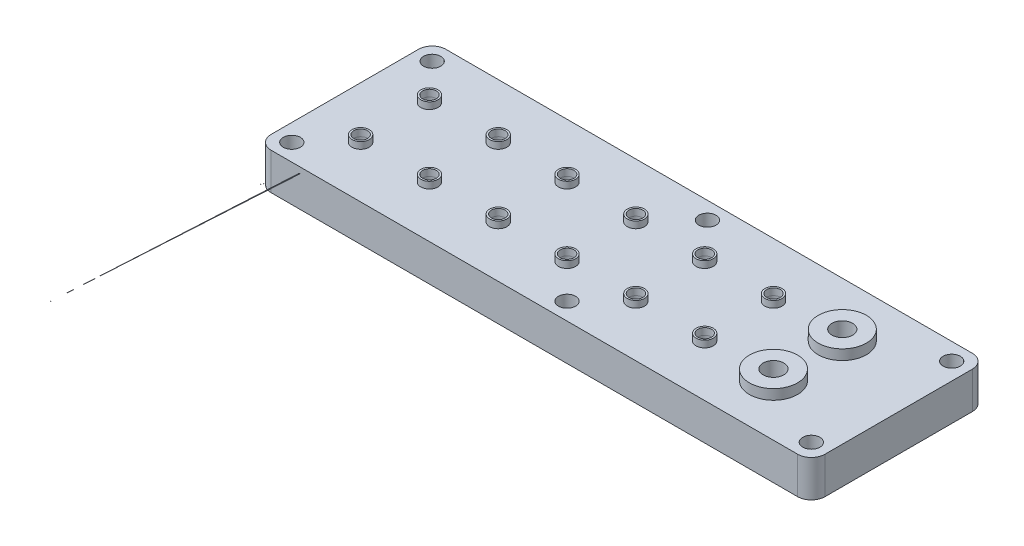
SolidWorks part; units mm, degrees
material "PE High Density"
ref_plane "Front Plane" through (0, 0, 0) normal (0, 0, 1) x (1, 0, 0)
ref_plane "Top Plane" through (0, 0, 0) normal (0, 1, 0) x (1, 0, 0)
ref_plane "Right Plane" through (0, 0, 0) normal (1, 0, 0) x (0, 0, -1)
sketch "Sketch1" plane through (0, 0, 0) normal (0, 1, 0) x (1, 0, 0)
  line L1 (0, 0) -> (161, 0)
  line L2 (0, 0) -> (0, 50.8)
  line L3 (0, 50.8) -> (161, 50.8)
  line L4 (161, 0) -> (161, 50.8)
  dimension "D1" = 161
  dimension "D2" = 50.8
extrude "Boss-Extrude1" add sketch "Sketch1" along normal blind 10.7
sketch "Sketch2" plane through (0, 10.7, 0) normal (0, 1, 0) x (1, 0, 0)
  line L0 (0, 50.8) -> (0, 0) construction
  line L2 (0, 0) -> (161, 0) construction
  circle A0 centre (15, 15) radius 2
  circle A1 centre (15, 35) radius 2
  circle A2 centre (35, 15) radius 2
  circle A3 centre (35, 35) radius 2
  circle A4 centre (55, 35) radius 2
  circle A5 centre (55, 15) radius 2
  circle A6 centre (75, 35) radius 2
  circle A7 centre (75, 15) radius 2
  circle A8 centre (95, 35) radius 2
  circle A9 centre (95, 15) radius 2
  circle A10 centre (115, 35) radius 2
  circle A11 centre (115, 15) radius 2
  circle A12 centre (135, 35) radius 2
  circle A13 centre (135, 15) radius 2
  dimension "D1" = 4
  dimension "D4" = 20
  dimension "D8" = 20
  dimension "D30" = 4
  dimension "D31" = 4
  dimension "D32" = 4
  dimension "D33" = 4
  dimension "D34" = 4
  dimension "D35" = 4
  dimension "D36" = 4
  dimension "D37" = 4
  dimension "D38" = 4
  dimension "D39" = 4
  dimension "D40" = 4
  dimension "D41" = 4
  dimension "D42" = 4
  dimension "D2" = 15
  dimension "D3" = 15
  dimension "D5" = 15
  dimension "D6" = 20
  dimension "D7" = 15
  dimension "D9" = 20
  dimension "D10" = 20
  dimension "D11" = 20
  dimension "D12" = 20
  dimension "D13" = 20
  dimension "D14" = 20
  dimension "D15" = 20
  dimension "D16" = 15
  dimension "D17" = 15
  dimension "D18" = 20
  dimension "D19" = 15
  dimension "D20" = 20
  dimension "D21" = 20
  dimension "D22" = 20
  dimension "D23" = 20
  dimension "D24" = 20
  dimension "D25" = 15
  dimension "D26" = 20
  dimension "D27" = 20
  dimension "D28" = 20
  dimension "D29" = 15
extrude "Cut-Extrude2" cut sketch "Sketch2" against normal through all and the other way blind 1.45
sketch "Sketch3" plane through (0, 0, 0) normal (0, -1, 0) x (-1, 0, 0)
  line L0 (0, 50.8) -> (0, 0) construction
  line L1 (-14.5, 12.5) -> (-135.5, 12.5)
  line L2 (-12.5, 14.5) -> (-12.5, 15.5)
  line L3 (-14.5, 17.5) -> (-135.5, 17.5)
  line L4 (-137.5, 14.5) -> (-137.5, 15.5)
  line L5 (-14.5, 32.5) -> (-135.5, 32.5)
  line L6 (-12.5, 34.5) -> (-12.5, 35.5)
  line L7 (-14.5, 37.5) -> (-135.5, 37.5)
  line L8 (-137.5, 34.5) -> (-137.5, 35.5)
  line L10 (-161, 50.8) -> (0, 50.8) construction
  arc A0 (-14.5, 12.5) -> (-12.5, 14.5) centre (-14.5, 14.5) ccw
  arc A1 (-12.5, 15.5) -> (-14.5, 17.5) centre (-14.5, 15.5) ccw
  arc A2 (-14.5, 32.5) -> (-12.5, 34.5) centre (-14.5, 34.5) ccw
  arc A3 (-12.5, 35.5) -> (-14.5, 37.5) centre (-14.5, 35.5) ccw
  arc A4 (-135.5, 37.5) -> (-137.5, 35.5) centre (-135.5, 35.5) ccw
  arc A5 (-137.5, 34.5) -> (-135.5, 32.5) centre (-135.5, 34.5) ccw
  arc A6 (-137.5, 15.5) -> (-135.5, 17.5) centre (-135.5, 15.5) cw
  arc A7 (-135.5, 12.5) -> (-137.5, 14.5) centre (-135.5, 14.5) cw
  point P14 (-12.5, 12.5)
  point P17 (-12.5, 17.5)
  point P20 (-12.5, 32.5)
  point P23 (-12.5, 37.5)
  dimension "D2" = 33.3
  dimension "D7" = 2
  dimension "D1" = 5
  dimension "D3" = 13.3
  dimension "D4" = 12.5
  dimension "D5" = 137.5
  dimension "D6" = 5
  dimension "D9" = 12.5
  dimension "D10" = 137.5
extrude "Cut-Extrude3" cut sketch "Sketch3" against normal blind 3.5
sketch "Sketch4" plane through (0, 10.7, 0) normal (0, 1, 0) x (1, 0, 0)
  circle A0 centre (15, 35) radius 2.5
  circle A1 centre (15, 15) radius 2.5
  circle A2 centre (35, 35) radius 2.5
  circle A3 centre (35, 15) radius 2.5
  circle A4 centre (55, 35) radius 2.5
  circle A5 centre (55, 15) radius 2.5
  circle A6 centre (75, 35) radius 2.5
  circle A7 centre (75, 15) radius 2.5
  circle A8 centre (95, 35) radius 2.5
  circle A9 centre (115, 15) radius 2.5
  circle A10 centre (115, 35) radius 2.5
  circle A11 centre (95, 15) radius 2.5
  circle A12 centre (135, 15) radius 6.9983
  circle A13 centre (135, 35) radius 7
  dimension "D1" = 5
  dimension "D2" = 5
  dimension "D3" = 5
  dimension "D4" = 5
  dimension "D5" = 5
  dimension "D6" = 5
  dimension "D7" = 5
  dimension "D8" = 5
  dimension "D9" = 5
  dimension "D10" = 5
  dimension "D11" = 5
  dimension "D12" = 5
  dimension "D13" = 14
  dimension "D14" = 13.9965
extrude "Boss-Extrude5" add sketch "Sketch4" along normal blind 1.95
sketch "Sketch6" plane through (0, 12.65, 0) normal (0, 1, 0) x (1, 0, 0)
  circle A0 centre (15.0119, 14.9967) radius 2
  circle A1 centre (15.0119, 34.9967) radius 2
  circle A2 centre (35.0119, 14.9967) radius 2
  circle A3 centre (35.0119, 34.9967) radius 2
  circle A4 centre (55.0119, 34.9967) radius 2
  circle A5 centre (55.0119, 14.9967) radius 2
  circle A6 centre (75.0119, 34.9967) radius 2
  circle A7 centre (75.0119, 14.9967) radius 2
  circle A8 centre (95.0119, 34.9967) radius 2
  circle A9 centre (95.0119, 14.9967) radius 2
  circle A10 centre (115.0119, 34.9967) radius 2
  circle A11 centre (115.0119, 14.9967) radius 2
  circle A12 centre (135.0119, 34.9967) radius 2
  circle A13 centre (135.0119, 14.9967) radius 2
extrude "Cut-Extrude5" cut sketch "Sketch6" against normal blind 1.95
sketch "Sketch7" plane through (0, 0, 0) normal (0, -1, 0) x (-1, 0, 0)
  line L0 (-6.5, 8.75) -> (-154.5, 8.75) construction
  line L1 (-6.5, 6.75) -> (-154.5, 6.75)
  line L2 (-6.5, 10.75) -> (-154.5, 10.75)
  line L3 (-6.5, 8.75) -> (-6.5, 21.25) construction
  line L4 (-8.5, 8.75) -> (-8.5, 21.25)
  line L5 (-4.5, 8.75) -> (-4.5, 21.25)
  line L6 (-6.5, 21.25) -> (-154.5, 21.25) construction
  line L7 (-6.5, 19.25) -> (-154.5, 19.25)
  line L8 (-6.5, 23.25) -> (-154.5, 23.25)
  line L9 (-154.5, 21.25) -> (-154.5, 8.75) construction
  line L10 (-152.5, 21.25) -> (-152.5, 8.75)
  line L11 (-156.5, 21.25) -> (-156.5, 8.75)
  line L13 (0, 50.8) -> (0, 0) construction
  line L14 (-6.5, 28.75) -> (-154.5, 28.75) construction
  line L15 (-6.5, 26.75) -> (-154.5, 26.75)
  line L16 (-6.5, 30.75) -> (-154.5, 30.75)
  line L17 (-6.5, 28.75) -> (-6.5, 41.25) construction
  line L18 (-8.5, 28.75) -> (-8.5, 41.25)
  line L19 (-4.5, 28.75) -> (-4.5, 41.25)
  line L20 (-6.5, 41.25) -> (-154.5, 41.25) construction
  line L21 (-6.5, 39.25) -> (-154.5, 39.25)
  line L22 (-6.5, 43.25) -> (-154.5, 43.25)
  line L23 (-154.5, 41.25) -> (-154.5, 28.75) construction
  line L24 (-152.5, 41.25) -> (-152.5, 28.75)
  line L25 (-156.5, 41.25) -> (-156.5, 28.75)
  line L27 (-161, 50.8) -> (0, 50.8) construction
  arc A0 (-6.5, 6.75) -> (-6.5, 10.75) centre (-6.5, 8.75) ccw
  arc A1 (-154.5, 10.75) -> (-154.5, 6.75) centre (-154.5, 8.75) ccw
  arc A2 (-8.5, 8.75) -> (-4.5, 8.75) centre (-6.5, 8.75) ccw
  arc A3 (-4.5, 21.25) -> (-8.5, 21.25) centre (-6.5, 21.25) ccw
  arc A4 (-6.5, 19.25) -> (-6.5, 23.25) centre (-6.5, 21.25) ccw
  arc A5 (-154.5, 23.25) -> (-154.5, 19.25) centre (-154.5, 21.25) ccw
  arc A6 (-152.5, 21.25) -> (-156.5, 21.25) centre (-154.5, 21.25) ccw
  arc A7 (-156.5, 8.75) -> (-152.5, 8.75) centre (-154.5, 8.75) ccw
  arc A8 (-6.5, 26.75) -> (-6.5, 30.75) centre (-6.5, 28.75) ccw
  arc A9 (-154.5, 30.75) -> (-154.5, 26.75) centre (-154.5, 28.75) ccw
  arc A10 (-8.5, 28.75) -> (-4.5, 28.75) centre (-6.5, 28.75) ccw
  arc A11 (-4.5, 41.25) -> (-8.5, 41.25) centre (-6.5, 41.25) ccw
  arc A12 (-6.5, 39.25) -> (-6.5, 43.25) centre (-6.5, 41.25) ccw
  arc A13 (-154.5, 43.25) -> (-154.5, 39.25) centre (-154.5, 41.25) ccw
  arc A14 (-152.5, 41.25) -> (-156.5, 41.25) centre (-154.5, 41.25) ccw
  arc A15 (-156.5, 28.75) -> (-152.5, 28.75) centre (-154.5, 28.75) ccw
  point P2 (-80.5, 8.75)
  point P7 (-6.5, 15)
  point P14 (-80.5, 21.25)
  point P21 (-154.5, 15)
  point P34 (-80.5, 28.75)
  point P39 (-6.5, 35)
  point P46 (-80.5, 41.25)
  point P53 (-154.5, 35)
  dimension "D10" = 22.05
  dimension "D5" = 9.55
  dimension "D11" = 154.5
  dimension "D4" = 42.05
  dimension "D2" = 154.5
  dimension "D3" = 29.55
  dimension "D7" = 6.5
  dimension "D9" = 6.5
extrude "Cut-Extrude7" cut sketch "Sketch7" against normal blind 3.22 contours L1 A1 L2 A0 | L11 A7 L10 A6 | L7 A5 L8 A4 | L4 A3 L5 A2 | L18 A11 L19 A10 | L16 A9 L15 A8 | L21 A13 L22 A12 | L24 A15 L25 A14
fillet "Fillet1" radius 4 4 edges at (161, 5.35, -50.8) (161, 5.35, 0) (0, 5.35, 0) (0, 5.35, -50.8)
hole_wizard "Ø5.0mm Dowel Hole1" positions "Sketch9" profile "Sketch8" hole size "Ø5.0" standard "ANSI Metric" end condition through all
sketch "Sketch9" plane through (0, 0, 0) normal (0, -1, 0) x (-1, 0, 0)
  line L0 (-157, 50.8) -> (-4, 50.8) construction
  line L1 (0, 46.8) -> (0, 4) construction
  point P0 (-5, 45.8)
  point P2 (-85, 45.8)
  point P4 (-156, 45.8)
  point P6 (-156, 5)
  point P8 (-85, 5)
  point P10 (-5, 5)
  dimension "D1" = 5
  dimension "D2" = 5
  dimension "D3" = 85
  dimension "D4" = 156
  dimension "D5" = 45.8
sketch "Sketch8" plane through (5, 0, -45.8) normal (1, 0, 0) x (0, 0, -1)
  line L0 (0, 0) -> (0, 12.65)
  line L1 (0, 12.65) -> (2.5, 12.65)
  line L2 (2.5, 12.65) -> (2.5, 0)
  line L5 (2.5, 0) -> (0, 0)
  line L11 (0, -6.35) -> (0, 107.95) construction
  dimension "Thru Hole Dia." = 5
  dimension "Thru Hole Depth" = 12.65
sketch "Sketch10" plane through (0, 12.65, 0) normal (0, 1, 0) x (1, 0, 0)
  circle A0 centre (135, 35) radius 7 construction
  circle A1 centre (135, 15) radius 6.9983 construction
  circle A2 centre (135, 35) radius 7
  circle A3 centre (135, 15) radius 6.9983
extrude "Boss-Extrude6" add sketch "Sketch10" along normal blind 1
hole_wizard "Ø6.0mm Dowel Hole1" positions "Sketch12" profile "Sketch11" hole size "Ø6.0" standard "ANSI Metric"
sketch "Sketch12" plane through (0, 13.65, 0) normal (0, 1, 0) x (1, 0, 0)
  point P0 (135, 35)
  point P3 (135, 15)
sketch "Sketch11" plane through (135, 13.65, -35) normal (1, 0, 0) x (0, 0, 1)
  line L0 (0, 0) -> (0, 8.8026)
  line L1 (0, 8.8026) -> (3, 7)
  line L2 (3, 7) -> (3, 0)
  line L5 (3, 0) -> (0, 0)
  line L10 (0, 8.8026) -> (-3, 7) construction
  line L11 (0, -6.35) -> (0, 107.95) construction
  dimension "Hole Dia." = 6
  dimension "Hole Depth" = 7
  dimension "Drill Angle" = 118
